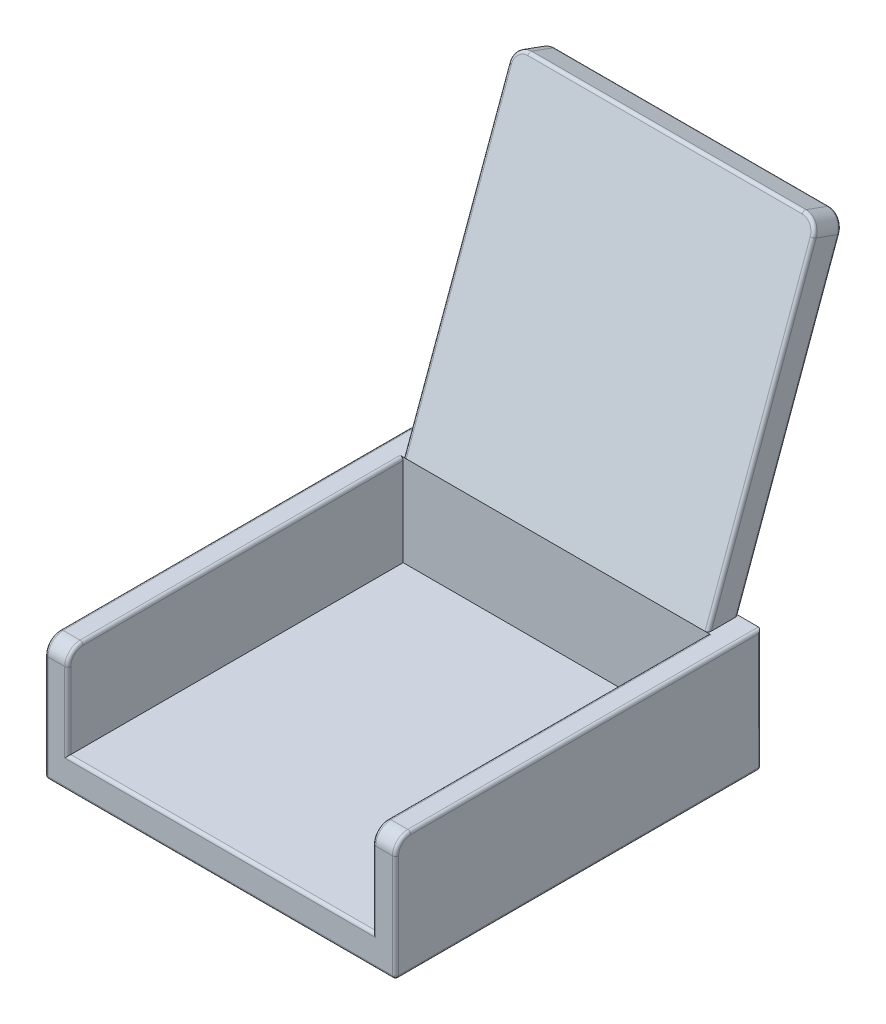
SolidWorks part; units mm, degrees
ref_plane "前视基准面" through (0, 0, 0) normal (0, 0, 1) x (1, 0, 0)
ref_plane "上视基准面" through (0, 0, 0) normal (0, 1, 0) x (1, 0, 0)
ref_plane "右视基准面" through (0, 0, 0) normal (1, 0, 0) x (0, 0, -1)
sketch "草图1" plane through (0, 0, 0) normal (0, 1, 0) x (1, 0, 0)
  line L0 (11.5, 12) -> (11.5, -12)
  line L1 (11.5, 12) -> (-11.5, 12)
  line L2 (11.5, -12) -> (-11.5, -12)
  line L3 (-11.5, 12) -> (-11.5, -12)
  line L4 (11.5, 12) -> (-11.5, -12) construction
  line L5 (11.5, -12) -> (-11.5, 12) construction
  point P1 (0, 0)
  dimension "D1" = 23
  dimension "D2" = 24
extrude "凸台-拉伸1" add sketch "草图1" along normal blind 8
sketch "草图2" plane through (0, 8, 0) normal (0, 1, 0) x (1, 0, 0)
  line L0 (-11.5, -12) -> (11.5, -12) construction
  line L1 (-10, -12) -> (10, -12)
  line L2 (-10, -12) -> (-10, 10)
  line L3 (-10, 10) -> (10, 10)
  line L4 (10, -12) -> (10, 10)
  line L5 (-11.5, 12) -> (-11.5, -12) construction
  line L6 (11.5, -12) -> (11.5, 12) construction
  line L7 (11.5, 12) -> (-11.5, 12) construction
  dimension "D1" = 1.5
  dimension "D2" = 1.5
  dimension "D3" = 2
extrude "切除-拉伸1" cut sketch "草图2" against normal blind 6
sketch "草图3" plane through (0, 0, 0) normal (1, 0, 0) x (0, 0, -1)
  line L0 (12, 8) -> (19.0114, 27.2637)
  line L1 (-12, 8) -> (12, 8) construction
  line L2 (10, 8) -> (17.2454, 27.9065)
  line L3 (12, 8) -> (10, 8)
  line L4 (10.234, 8.6428) -> (17.2454, 27.9065) construction
  line L5 (17.2454, 27.9065) -> (19.0114, 27.2637)
  line L6 (12, 8) -> (12, 0) construction
  dimension "D1" = 110
  dimension "D2" = 20.5
  dimension "D3" = 90
  dimension "D4" = 2
extrude "凸台-拉伸3" add sketch "草图3" along normal blind 10 and the other way blind 10
sketch "草图4" plane through (0, 0, 12) normal (0, 0, 1) x (1, 0, 0)
  line L0 (0, 0) -> (0, -2) construction
  line L1 (0, -2) -> (0, -2.5) construction
  line L2 (-1.5, 0) -> (1.5, 0)
  line L3 (-11.5, 0) -> (11.5, 0) construction
  line L4 (1.5, 0) -> (1.5, -0.6771)
  line L5 (1.466, -2.5) -> (1.95, -2.5)
  line L6 (1.95, -2.5) -> (1.95, -1.5556)
  line L7 (0, 0) -> (0, -1) construction
  line L8 (-0.6, -1) -> (0.6, -1)
  line L9 (0.6, -1) -> (1.466, -2.5)
  line L10 (-0.6, -1) -> (-1.466, -2.5)
  line L11 (-1.466, -2.5) -> (-1.95, -2.5)
  line L12 (-1.95, -2.5) -> (-1.95, -1.5556)
  line L13 (-1.5, 0) -> (-1.5, -0.6771)
  arc A0 (1.95, -1.5556) -> (1.5, -0.6771) centre (0, -2) ccw
  arc A1 (-1.95, -1.5556) -> (-1.5, -0.6771) centre (0, -2) cw
  dimension "D1" = 2
  dimension "D2" = 0.5
  dimension "D3" = 1.5
  dimension "D4" = 1.95
  dimension "D5" = 1
  dimension "D6" = 0.6
  dimension "D7" = 30
extrude "凸台-拉伸4" add sketch "草图4" against normal blind 15 from offset 3.5 offset against normal yes
fillet "圆角1" radius 1 4 edges at (-10, 27.5851, -18.1284) (10, 27.5851, -18.1284) (10.75, 8, 12) (-10.75, 8, 12)
fillet "圆角3" radius 0.2 19 edges at (-10, 8, 0.5) (-10, 7.7071, 11.7071) (10, 8, 0.5) (10, 7.7071, 11.7071) (-11.5, 0, 0) (-11.5, 4, -12) (-11.5, 8, -0.5) (-11.5, 7.7071, 11.7071) (11.5, 4, -12) (11.5, 0, 0) (11.5, 7.7071, 11.7071) (11.5, 8, -0.5) (0, 0, 12) (-11.5, 3.5, 12) (-10, 4.5, 12) (0, 2, 12) (10, 4.5, 12) (11.5, 3.5, 12) (0, 0, -12)
fillet "圆角4" radius 0.2 10 edges at (-9.7071, 26.9885, -18.9112) (0, 27.2637, -19.0114) (9.7071, 26.9885, -18.9112) (-10, 17.4834, -13.4517) (-9.7071, 27.6313, -17.1452) (0, 27.9065, -17.2454) (9.7071, 27.6313, -17.1452) (10, 17.4834, -13.4517)
fillet "圆角6" radius 0.1 8 edges at (1.95, -2.5, 1) (1.708, -2.5, -6.5) (1.466, -2.5, 1) (1.708, -2.5, 8.5) (-1.466, -2.5, 1) (-1.708, -2.5, -6.5) (-1.95, -2.5, 1) (-1.708, -2.5, 8.5)
